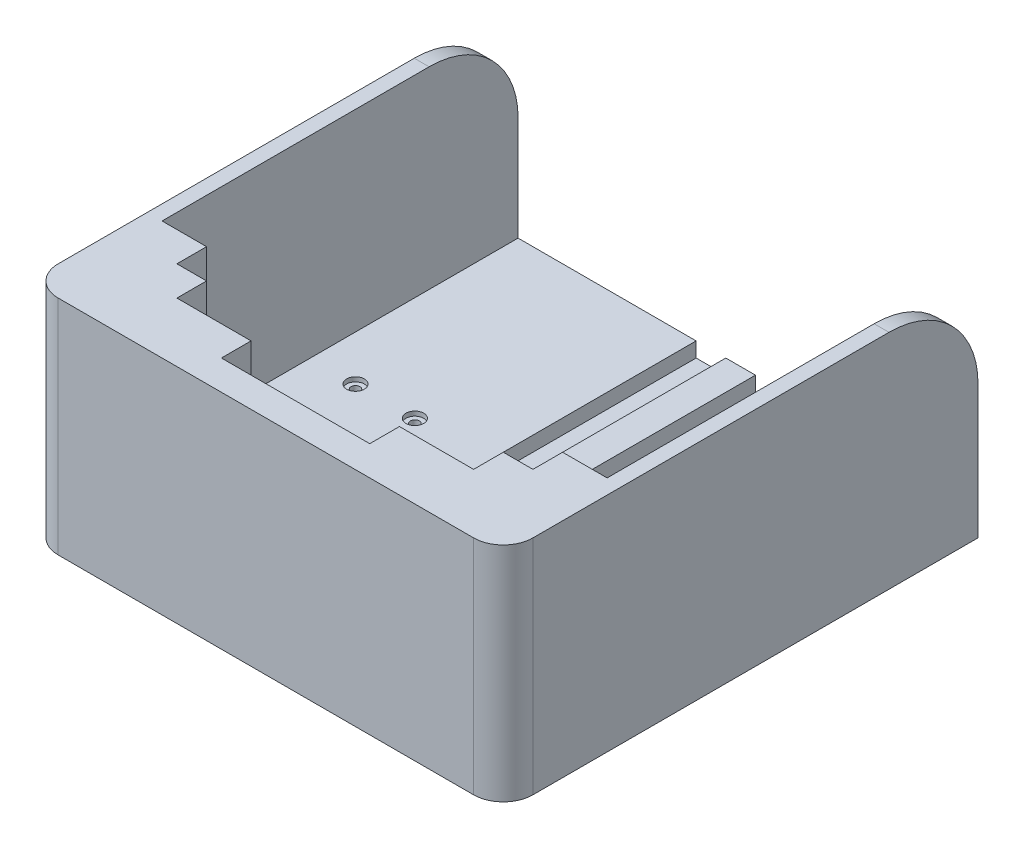
SolidWorks part; units mm, degrees
ref_plane "Front Plane" through (0, 0, 0) normal (0, 0, 1) x (1, 0, 0)
ref_plane "Top Plane" through (0, 0, 0) normal (0, 1, 0) x (1, 0, 0)
ref_plane "Right Plane" through (0, 0, 0) normal (1, 0, 0) x (0, 0, -1)
sketch "Sketch1" plane through (0, 0, 0) normal (0, 1, 0) x (1, 0, 0)
  line L1 (-80, 80) -> (80, 80)
  line L2 (-80, 80) -> (-80, -80)
  line L3 (-80, -80) -> (80, -80)
  line L4 (80, 80) -> (80, -80)
  line L5 (-80, 80) -> (80, -80) construction
  line L6 (-80, -80) -> (80, 80) construction
  point P0 (0, 0)
  dimension "D1" = 160
  dimension "D2" = 160
extrude "Boss-Extrude1" add sketch "Sketch1" along normal blind 75
sketch "Sketch2" plane through (0, 75, 0) normal (0, 1, 0) x (1, 0, 0)
  line L0 (-80, 80) -> (-80, -80) construction
  line L2 (-75, 80) -> (75, 80)
  line L4 (-75, 80) -> (-75, -70)
  line L5 (-75, -70) -> (75, -70)
  line L6 (75, 80) -> (75, -70)
  line L7 (80, -80) -> (80, 80) construction
  line L8 (80, 80) -> (-80, 80) construction
  line L9 (-80, -80) -> (80, -80) construction
  point P6 (0, 0)
  point P13 (0, 0)
  dimension "D1" = 5
  dimension "D2" = 5
  dimension "D3" = 0
  dimension "D4" = 10
extrude "Cut-Extrude1" cut sketch "Sketch2" against normal offset from surface (65 mm away) 10 up to face at (0, 0, 0)
sketch "Sketch3" plane through (0, 0, 70) normal (0, 0, -1) x (-1, 0, 0)
  line L0 (-75, 10) -> (75, 10) construction
  line L1 (-75, 75) -> (-60, 75)
  line L2 (-75, 75) -> (-75, 10)
  line L3 (-75, 10) -> (-60, 10)
  line L4 (-60, 75) -> (-60, 10)
  line L5 (0, 75) -> (0, 10) construction
  line L6 (75, 75) -> (-75, 75) construction
  line L7 (75, 10) -> (60, 10)
  line L8 (60, 75) -> (60, 10)
  line L9 (75, 75) -> (60, 75)
  line L10 (75, 75) -> (75, 10)
  dimension "D1" = 15
extrude "Boss-Extrude2" add sketch "Sketch3" along normal blind 30
sketch "Sketch4" plane through (0, 0, 70) normal (0, 0, -1) x (-1, 0, 0)
  line L0 (0, 75) -> (0, 10) construction
  line L1 (60, 75) -> (-60, 75) construction
  line L2 (75, 10) -> (-75, 10) construction
  line L3 (-60, 10) -> (60, 10) construction
  line L4 (-60, 75) -> (-50, 75)
  line L5 (-60, 75) -> (-60, 10)
  line L6 (-60, 10) -> (-50, 10)
  line L7 (-50, 75) -> (-50, 10)
  line L8 (60, 10) -> (50, 10)
  line L9 (50, 75) -> (50, 10)
  line L10 (60, 75) -> (50, 75)
  line L11 (60, 75) -> (60, 10)
  dimension "D1" = 10
extrude "Boss-Extrude3" add sketch "Sketch4" along normal blind 20
fillet "Fillet1" radius 10 2 edges at (80, 37.5, 80) (-80, 37.5, 80)
sketch "Sketch11" plane through (0, 0, 70) normal (0, 0, -1) x (-1, 0, 0)
  line L0 (-50, 10) -> (50, 10) construction
  line L1 (-50, 75) -> (-25, 75)
  line L2 (-50, 75) -> (-50, 10)
  line L3 (-50, 10) -> (-25, 10)
  line L4 (-25, 75) -> (-25, 10)
  line L5 (0, 75) -> (0, 10) construction
  line L6 (50, 75) -> (-50, 75) construction
  line L7 (75, 10) -> (-75, 10) construction
  line L8 (50, 10) -> (25, 10)
  line L9 (25, 75) -> (25, 10)
  line L10 (50, 75) -> (25, 75)
  line L11 (50, 75) -> (50, 10)
  dimension "D1" = 25
extrude "Boss-Extrude4" add sketch "Sketch11" along normal blind 10
fillet "Fillet2" radius 30 2 edges at (-77.5, 75, -80) (77.5, 75, -80)
sketch "Sketch15" plane through (0, 0, 0) normal (0, -1, 0) x (1, 0, 0)
  line L0 (-80, 0) -> (80, 0) construction
  line L1 (80, 70) -> (80, -80) construction
  line L2 (0, 0) -> (0, 80) construction
  line L3 (-70, 80) -> (70, 80) construction
  circle A0 centre (-59.8059, 10) radius 1.5
  circle A1 centre (-39.8059, 10) radius 1.5
  circle A2 centre (39.8059, 10) radius 1.5
  circle A3 centre (59.8059, 10) radius 1.5
  circle A4 centre (59.8059, -10) radius 1.5
  circle A5 centre (39.8059, -10) radius 1.5
  circle A6 centre (-39.8059, -10) radius 1.5
  circle A7 centre (-59.8059, -10) radius 1.5
  point P6 (0, 0)
  dimension "D1" = 3
  dimension "D2" = 3
  dimension "D3" = 20
  dimension "D4" = 10
extrude "Cut-Extrude2" cut sketch "Sketch15" against normal up to surface (10 mm away) up to face at (0, 10, 36.25)
sketch "Sketch17" plane through (0, 10, 0) normal (0, 1, 0) x (1, 0, 0)
  line L0 (-59.8059, 10) -> (-39.8059, 10) construction
  line L1 (-39.8059, 10) -> (-39.8059, -10) construction
  line L2 (-49.8059, 10) -> (-49.8059, -10) construction
  line L3 (-39.8059, 0) -> (-59.8059, 0) construction
  line L4 (0, 24.5779) -> (0, -24.5779) construction
  circle A1 centre (-59.8059, 10) radius 3
  circle A2 centre (-39.8059, 10) radius 3
  circle A3 centre (-39.8059, -10) radius 3
  circle A4 centre (-59.8059, -10) radius 3
  circle A5 centre (39.8059, -10) radius 3
  circle A6 centre (59.8059, -10) radius 3
  circle A7 centre (39.8059, 10) radius 3
  circle A8 centre (59.8059, 10) radius 3
  point P19 (0, 0)
  dimension "D1" = 6
extrude "Cut-Extrude3" cut sketch "Sketch17" against normal blind 1.5
sketch "Sketch18" plane through (0, 10, 0) normal (0, 1, 0) x (1, 0, 0)
  line L0 (0, 80) -> (0, -70) construction
  line L1 (-75, 80) -> (75, 80) construction
  line L2 (25, -70) -> (-25, -70) construction
  line L3 (-25, -70) -> (25, -70) construction
  line L4 (5, 80) -> (15, 80)
  line L5 (5, 80) -> (5, -65)
  line L6 (5, -65) -> (15, -65)
  line L7 (15, 80) -> (15, -65)
  line L8 (-5, -65) -> (-15, -65)
  line L9 (-15, 80) -> (-15, -65)
  line L10 (-5, 80) -> (-15, 80)
  line L11 (-5, 80) -> (-5, -65)
  dimension "D1" = 10
  dimension "D2" = 0
  dimension "D3" = 10
  dimension "D4" = 5
extrude "Cut-Extrude6" cut sketch "Sketch18" against normal blind 5
